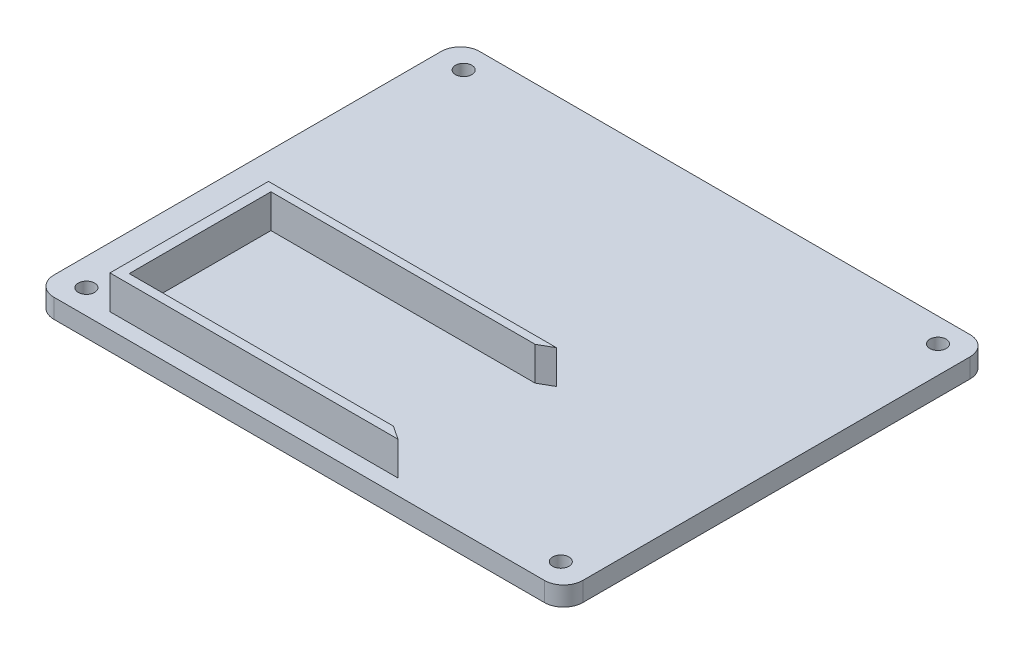
SolidWorks part; units mm, degrees
note: The reader was unsure of these and kept them because the rebuilt part matched: shared geometry of "Sketch1<3>".
ref_plane "Front Plane" through (0, 0, 0) normal (0, 0, 1) x (1, 0, 0)
ref_plane "Top Plane" through (0, 0, 0) normal (0, 1, 0) x (1, 0, 0)
ref_plane "Right Plane" through (0, 0, 0) normal (1, 0, 0) x (0, 0, -1)
sketch "Sketch1" plane through (0, 0, 0) normal (0, 1, 0) x (1, 0, 0)
  line L0 (0, 0) -> (0, 83.51) construction
  line L7 (55.045, 79.51) -> (55.045, -1.09)
  line L8 (-55.045, 79.51) -> (-55.045, -1.09)
  line L9 (-51.045, -5.09) -> (51.045, -5.09)
  line L10 (51.045, 83.51) -> (-51.045, 83.51)
  line L11 (14.5352, 29.5) -> (17.3466, 31.1086)
  line L12 (-40.4648, 0) -> (14.5352, 0)
  line L13 (-40.4648, 0) -> (-40.4648, 29.5)
  line L14 (-40.4648, 29.5) -> (14.5352, 29.5)
  line L16 (-42.5928, -1.8758) -> (17.3466, -1.8758)
  line L17 (-42.5928, -1.8758) -> (-42.5928, 31.1086)
  line L18 (-42.5928, 31.1086) -> (17.3466, 31.1086)
  line L20 (14.5352, 0) -> (17.3466, -1.8758)
  circle A0 centre (-49.365, 78.51) radius 1.7
  circle A1 centre (-49.365, 0) radius 1.7
  circle A2 centre (49.365, 0) radius 1.7
  circle A3 centre (49.365, 78.51) radius 1.7
  arc A4 (55.045, 79.51) -> (51.045, 83.51) centre (51.045, 79.51) ccw
  arc A5 (55.045, -1.09) -> (51.045, -5.09) centre (51.045, -1.09) cw
  arc A6 (-55.045, -1.09) -> (-51.045, -5.09) centre (-51.045, -1.09) ccw
  arc A7 (-51.045, 83.51) -> (-55.045, 79.51) centre (-51.045, 79.51) ccw
  point P14 (0, -5.09)
  point P26 (55.045, 83.51)
  point P29 (55.045, -5.09)
  point P32 (-55.045, -5.09)
  point P35 (-55.045, 83.51)
  point P36 (0, 0)
  point P37 (0, 0)
  dimension "D4" = 55
  dimension "D5" = 4
  dimension "D1" = 29.5
  dimension "D2" = 5.68
  dimension "D6" = 5.09
extrude "Boss-Extrude1" add sketch "Sketch1" along normal blind 11 contours L17 L18 L11 L14 L13 L12 L20 L16
extrude "Boss-Extrude2" add sketch "Sketch1<3>" along normal blind 4 contours L7 L9 L8 L10
sketch "Sketch1<3>" plane through (0, 0, 0) normal (0, 1, 0) x (1, 0, 0) same geometry as "Sketch1"
